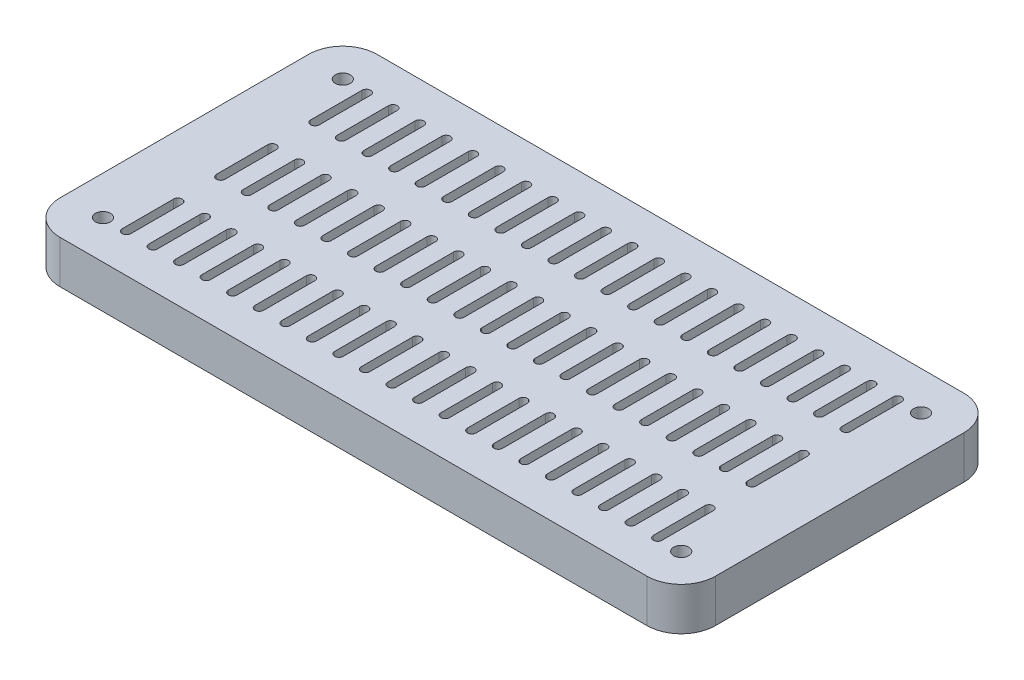
SolidWorks part; units mm, degrees
note: The reader was unsure of these and kept them because the rebuilt part matched: shared geometry of "Sketch1<3>".
ref_plane "Front Plane" through (0, 0, 0) normal (0, 0, 1) x (1, 0, 0)
ref_plane "Top Plane" through (0, 0, 0) normal (0, 1, 0) x (1, 0, 0)
ref_plane "Right Plane" through (0, 0, 0) normal (1, 0, 0) x (0, 0, -1)
sketch "Sketch1" plane through (0, 0, 0) normal (0, 1, 0) x (1, 0, 0)
  line L0 (-39.5, 0) -> (39.5, 0) construction
  line L1 (-39.5, 27) -> (39.5, 27)
  line L2 (-39.5, -27) -> (39.5, -27)
  line L3 (0, -6) -> (0, 6) construction
  line L4 (-76.5, -37) -> (76.5, -37)
  line L5 (-76.5, -37) -> (-76.5, 37)
  line L6 (-76.5, 37) -> (76.5, 37)
  line L7 (76.5, -37) -> (76.5, 37)
  line L8 (-76.5, -37) -> (76.5, 37) construction
  line L9 (-76.5, 37) -> (76.5, -37) construction
  line L10 (-1, -6) -> (-1, 6)
  line L11 (1, -6) -> (1, 6)
  arc A0 (-39.5, 27) -> (-39.5, -27) centre (-39.5, 0) ccw
  arc A1 (39.5, -27) -> (39.5, 27) centre (39.5, 0) ccw
  arc A2 (-1, -6) -> (1, -6) centre (0, -6) ccw
  arc A3 (1, 6) -> (-1, 6) centre (0, 6) ccw
  point P2 (0, 0)
  point P8 (-66.5, 0)
  point P9 (66.5, 0)
  point P10 (0, 0)
  point P17 (0, 0)
  dimension "D1" = 54
  dimension "D2" = 133
  dimension "D3" = 10
  dimension "D4" = 10
  dimension "D5" = 2
  dimension "D6" = 12
extrude "Boss-Extrude1" add sketch "Sketch1" along normal blind 10 contours L4 L7 L6 L5 A1 L2 A0 L1 | L2 A1 L1 A0 A3 L11 A2 L10 | L11 A3 L10 A2
extrude "Cut-Extrude1" cut sketch "Sketch1<3>" along normal through all contours L11 A3 L10 A2
sketch "Sketch1<3>" plane through (0, 0, 0) normal (0, 1, 0) x (1, 0, 0) same geometry as "Sketch1"
pattern_linear "LPattern1" count 11 spacing 6.2 along (1, 0, 0) count 2 spacing 22 along (0, 0, -1) of "Cut-Extrude1"
sketch "Sketch3" plane through (0, 10, 0) normal (0, 1, 0) x (1, 0, 0)
  line L0 (67.5, 37) -> (67.5, 28) construction
  line L1 (-76.5, 37) -> (76.5, 37) construction
  line L2 (67.5, 28) -> (76.5, 28) construction
  line L3 (76.5, -37) -> (76.5, 37) construction
  line L4 (67.5, 28) -> (62, 28) construction
  arc A0 (63, 28) -> (61, 28) centre (62, 28) ccw construction
  circle A1 centre (67.5, 28) radius 1.75
  dimension "D1" = 3.5
extrude "Cut-Extrude2" cut sketch "Sketch3" against normal through all
mirror "Mirror1" about plane through (0, 0, 0) normal (1, 0, 0) of "Cut-Extrude2", "LPattern1"
mirror "Mirror2" about plane through (0, 0, 0) normal (0, 0, 1) of "Mirror1", "LPattern1", "Cut-Extrude2"
fillet "Fillet1" radius 8 4 edges at (-76.5, 5, -37) (-76.5, 5, 37) (76.5, 5, 37) (76.5, 5, -37)
